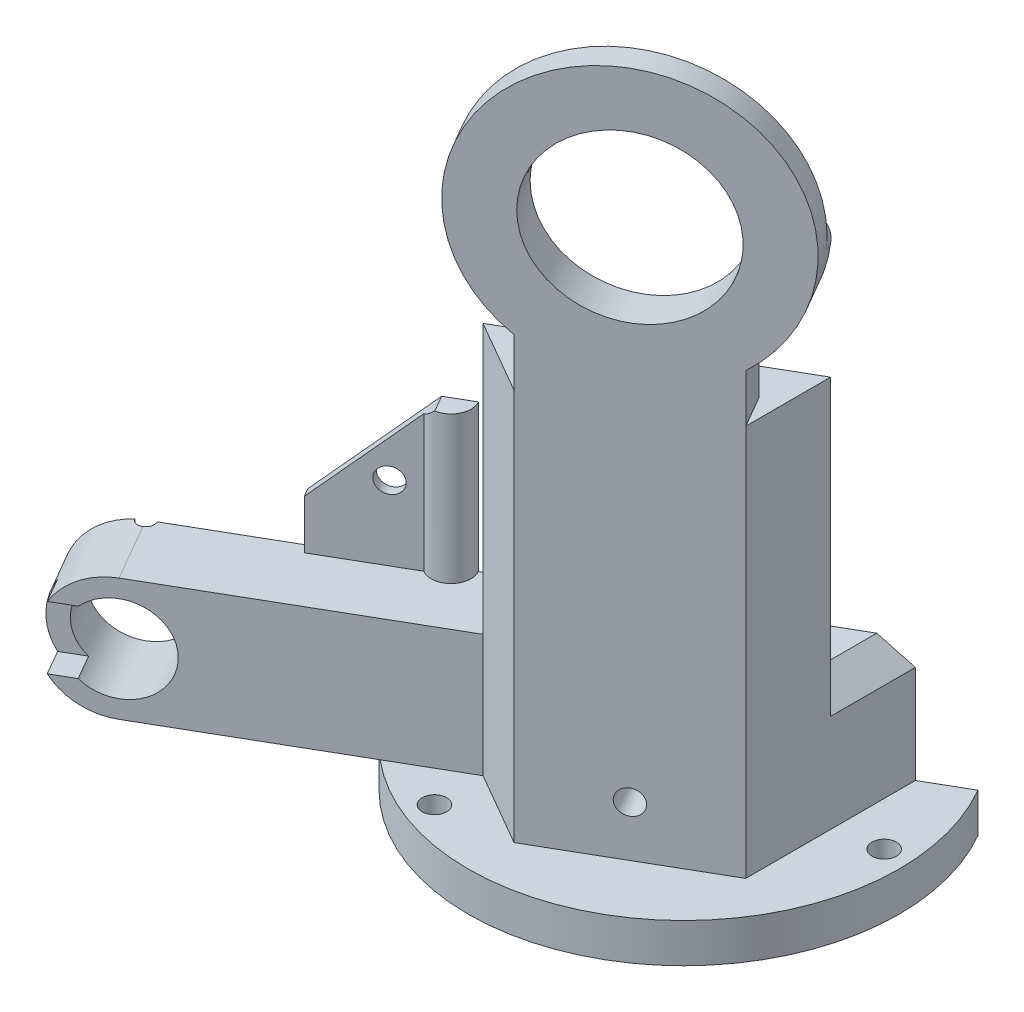
SolidWorks part; units mm, degrees
ref_plane "Front Plane" through (0, 0, 0) normal (0, 0, 1) x (1, 0, 0)
ref_plane "Top Plane" through (0, 0, 0) normal (0, 1, 0) x (1, 0, 0)
ref_plane "Right Plane" through (0, 0, 0) normal (1, 0, 0) x (0, 0, -1)
sketch "Sketch4" plane through (0, 0, 0) normal (0, 1, 0) x (1, 0, 0)
  circle A1 centre (0, 0) radius 55.88
  dimension "D2" = 111.76
extrude "Boss-Extrude2" add sketch "Sketch4" along normal blind 10.16
sketch "Sketch8" plane through (0, 10.16, 0) normal (0, 1, 0) x (1, 0, 0)
  line L1 (0, 43.9941) -> (-38.1, 21.997)
  line L2 (-38.1, 21.997) -> (-38.1, -21.997)
  line L3 (-38.1, -21.997) -> (0, -43.9941)
  line L4 (0, -43.9941) -> (38.1, -21.997)
  line L5 (38.1, -21.997) -> (38.1, 21.997)
  line L6 (38.1, 21.997) -> (0, 43.9941)
  circle A0 centre (0, 0) radius 38.1 construction
  dimension "D1" = 76.2
extrude "Boss-Extrude4" add sketch "Sketch8" along normal blind 101.6
sketch "Sketch9" plane through (-19.05, 0, -32.9956) normal (-0.5, 0, -0.866) x (-0.866, 0, 0.5)
  line L1 (21.997, 111.76) -> (-21.997, 111.76)
  line L2 (21.997, 111.76) -> (21.997, 124.226)
  line L4 (-21.997, 111.76) -> (-21.997, 124.226)
  arc A2 (21.997, 124.226) -> (-21.997, 124.226) centre (0, 152.4) ccw
extrude "Boss-Extrude5" add sketch "Sketch9" against normal blind 9.525
sketch "Sketch10" plane through (19.05, 0, 32.9956) normal (0.5, 0, 0.866) x (0.866, 0, -0.5)
  line L3 (-21.997, 111.76) -> (21.997, 111.76)
  line L4 (21.997, 111.76) -> (21.997, 124.226)
  line L5 (-21.997, 124.226) -> (-21.997, 111.76)
  line L6 (-21.997, 111.76) -> (21.997, 111.76)
  line L7 (21.997, 111.76) -> (21.997, 124.226)
  line L8 (-21.997, 124.226) -> (-21.997, 111.76)
  arc A1 (21.997, 124.226) -> (-21.997, 124.226) centre (0, 152.4) ccw
  arc A4 (21.997, 124.226) -> (-21.997, 124.226) centre (0, 152.4) ccw
  dimension "D1" = 0
extrude "Boss-Extrude6" add sketch "Sketch10" against normal blind 9.525
sketch "Sketch12" plane through (-19.05, 0, -32.9956) normal (-0.5, 0, -0.866) x (-0.866, 0, 0.5)
  circle A0 centre (0, 152.4) radius 21.5
  point P3 (0, 152.4)
  dimension "D1" = 43
extrude "Cut-Extrude4" cut sketch "Sketch12" against normal up to surface (76.2 mm away) up to face at (19.05, 92.7017, 32.9956)
sketch "Sketch13" plane through (-19.05, 0, 10.9985) normal (-0.866, 0, 0.5) x (0.5, 0, 0.866)
  line L0 (0, 111.76) -> (0, 10.16) construction
  line L1 (-19.05, 41.91) -> (19.05, 41.91)
  line L2 (-19.05, 41.91) -> (-19.05, 111.76)
  line L3 (-19.05, 111.76) -> (19.05, 111.76)
  line L4 (19.05, 41.91) -> (19.05, 111.76)
  line L5 (-19.05, 41.91) -> (19.05, 111.76) construction
  line L6 (-19.05, 111.76) -> (19.05, 41.91) construction
  line L7 (-38.1, 111.76) -> (0, 111.76) construction
  point P0 (0, 76.835)
  dimension "D1" = 69.85
  dimension "D2" = 0
  dimension "D3" = 38.1
extrude "Cut-Extrude5" cut sketch "Sketch13" against normal mid plane 152.4
sketch "Sketch14" plane through (-19.05, 0, -32.9956) normal (-0.5, 0, -0.866) x (-0.866, 0, 0.5)
  circle A0 centre (0, 124.7701) radius 3.8666
ref_plane "Plane1" through (0, 0, 0) normal (-0.5, 0, -0.866) x (-0.866, 0, 0.5)
sketch "Sketch17" plane through (0, 0, 0) normal (-0.5, 0, -0.866) x (-0.866, 0, 0.5)
  circle A0 centre (0, 152.4) radius 162.4584
  dimension "D1" = 324.9168
ref_plane "Plane3" through (38.1, 41.91, -21.997) normal (0, -1, 0) x (-1, 0, 0)
sketch "Sketch22" plane through (0, 0, 0) normal (-0.5, 0, -0.866) x (-0.866, 0, 0.5)
  line L5 (43.9941, 41.91) -> (102.101, 41.91)
  line L6 (102.101, 10.16) -> (43.9941, 10.16)
  line L8 (43.9941, 10.16) -> (21.997, 10.16)
  line L9 (21.997, 10.16) -> (21.997, 41.91)
  line L10 (21.997, 111.76) -> (21.997, 10.16) construction
  line L11 (21.997, 41.91) -> (43.9941, 41.91)
  arc A2 (102.101, 10.16) -> (102.101, 41.91) centre (102.101, 26.035) ccw
  circle A3 centre (0, 152.4) radius 162.4584 construction
  dimension "D1" = 31.75
ref_plane "Plane4" through (23.876, 0, 41.3544) normal (0.5, 0, 0.866) x (0.866, 0, -0.5)
extrude "Boss-Extrude10" add sketch "Sketch22" along normal mid plane 38.1
sketch "Sketch28" plane through (9.525, 0, 16.4978) normal (0.5, 0, 0.866) x (0.866, 0, -0.5)
  circle A0 centre (-102.101, 26.035) radius 11.2395
  dimension "D1" = 22.479
extrude "Cut-Extrude9" cut sketch "Sketch28" against normal up to surface (38.1 mm away) up to face at (-68.1724, 22.86, 17.3623)
sketch "Sketch29" plane through (9.525, 0, 16.4978) normal (0.5, 0, 0.866) x (0.866, 0, -0.5)
  line L1 (-104.4849, 17.907) -> (-122.1961, 17.907)
  line L2 (-104.4849, 17.907) -> (-104.4849, 34.163)
  line L3 (-104.4849, 34.163) -> (-122.1961, 34.163)
  line L4 (-122.1961, 17.907) -> (-122.1961, 34.163)
  line L5 (-104.4849, 17.907) -> (-122.1961, 34.163) construction
  line L6 (-104.4849, 34.163) -> (-122.1961, 17.907) construction
  circle A0 centre (-102.101, 26.035) radius 11.2395 construction
  arc A1 (-102.101, 41.91) -> (-102.101, 10.16) centre (-102.101, 26.035) ccw construction
  circle A2 centre (-102.101, 26.035) radius 11.2395
  circle A3 centre (-102.101, 26.035) radius 11.2395
  arc A4 (-102.101, 41.91) -> (-102.101, 10.16) centre (-102.101, 26.035) ccw
  point P0 (-113.3405, 26.035)
  circle M3 centre (-102.101, 26.035) radius 11.2395
  arc M7 (-102.101, 41.91) -> (-102.101, 10.16) centre (-102.101, 26.035) ccw
  dimension "D1" = 16.256
  dimension "D2" = 0
extrude "Cut-Extrude10" cut sketch "Sketch29" against normal blind 7.366 contours L3 L1 M3 M7 region at (-89.8086, 26.035, 73.8481)
chamfer "Chamfer1" distance 6.35 angle 45 2 edges at (38.1, 41.91, -10.9985) (28.575, 41.91, -27.4963)
sketch "Sketch30" plane through (0, 41.91, 0) normal (0, 1, 0) x (1, 0, 0)
  line L0 (-97.9471, -34.5527) -> (-78.8971, -67.5483) construction
  circle A0 centre (-88.4221, -51.0505) radius 2.1
  dimension "D1" = 4.2
extrude "Cut-Extrude11" cut sketch "Sketch30" against normal blind 7.366
sketch "Sketch31" plane through (0, 10.16, 0) normal (0, 1, 0) x (1, 0, 0)
  circle A0 centre (0, 0) radius 49.53 construction
  circle A4 centre (-49.089, 6.5948) radius 3.175
  circle A5 centre (26.9253, 41.5722) radius 3.175
  dimension "D1" = 6.35
  dimension "D2" = 99.06
  dimension "D3" = 6.35
extrude "Cut-Extrude12" cut sketch "Sketch31" against normal through all
mirror "Mirror1" about plane through (0, 0, 0) normal (-0.5, 0, -0.866) of "Cut-Extrude12"
sketch "Sketch33" plane through (0, 41.91, 0) normal (0, 1, 0) x (1, 0, 0)
  line L0 (140.6931, 81.2292) -> (-140.6931, -81.2292) construction
  line L5 (-43.4119, -22.0798) -> (-63.0924, -33.4424)
  line L6 (-63.0924, -33.4424) -> (-61.8003, -35.6804)
  line L7 (-61.8003, -35.6804) -> (-60.5427, -37.8586)
  line L8 (-60.5427, -37.8586) -> (-40.9154, -26.5041)
  arc A0 (-40.9154, -26.5041) -> (-43.4119, -22.0798) centre (-38.2434, -22.0798) ccw
extrude "Boss-Extrude11" add sketch "Sketch33" along normal blind 38.1
chamfer "Chamfer2" distance 25.4 angle 45 1 edges at (-61.8176, 80.01, 35.6505)
sketch "Sketch34" plane through (-1.2921, 0, -2.238) normal (-0.5, 0, -0.866) x (-0.866, 0, 0.5)
  circle A0 centre (55.1848, 61.1591) radius 3.175
  dimension "D1" = 6.35
extrude "Cut-Extrude13" cut sketch "Sketch34" against normal up to surface (5.0994 mm away) up to face at (-50.7291, 53.9288, 32.1813)
sketch "Sketch35" plane through (19.05, 0, 32.9956) normal (0.5, 0, 0.866) x (0.866, 0, -0.5)
  circle A0 centre (0, 23.2801) radius 3.175
  dimension "D1" = 6.35
extrude "Cut-Extrude14" cut sketch "Sketch35" against normal through all
sketch "Sketch36" plane through (-19.05, 0, 10.9985) normal (-0.866, 0, 0.5) x (0.5, 0, 0.866)
  line L0 (0, 0) -> (0, 199.814) construction
  line L1 (-31.75, 193.0158) -> (31.75, 193.0158)
  line L2 (-31.75, 193.0158) -> (-31.75, 156.3059)
  line L3 (-31.75, 156.3059) -> (31.75, 156.3059)
  line L4 (31.75, 193.0158) -> (31.75, 156.3059)
  line L5 (-55.88, 0) -> (55.88, 0) construction
  line L6 (0, 17.4625) -> (0, -17.4625) construction
  point P10 (0, 156.3059)
  dimension "D1" = 63.5
extrude "Cut-Extrude15" cut sketch "Sketch36" against normal mid plane 127
fillet "Fillet1" radius 6.35 6 edges at (-33.391, 156.3059, -15.5504) (3.2285, 156.3059, -36.6926) (15.6887, 156.3059, -43.8865) (45.8512, 156.3059, 8.3564) (-15.6887, 156.3059, 43.8865) (-45.8512, 156.3059, -8.3564)
sketch "Sketch37" plane through (0, 0, 0) normal (-0.5, 0, -0.866) x (-0.866, 0, 0.5)
  line L1 (-74.8839, -3.3145) -> (135.8585, -3.3145)
  line L2 (-74.8839, -3.3145) -> (-74.8839, 197.9105)
  line L3 (-74.8839, 197.9105) -> (135.8585, 197.9105)
  line L4 (135.8585, -3.3145) -> (135.8585, 197.9105)
extrude "Cut-Extrude16" cut sketch "Sketch37" along normal through all
